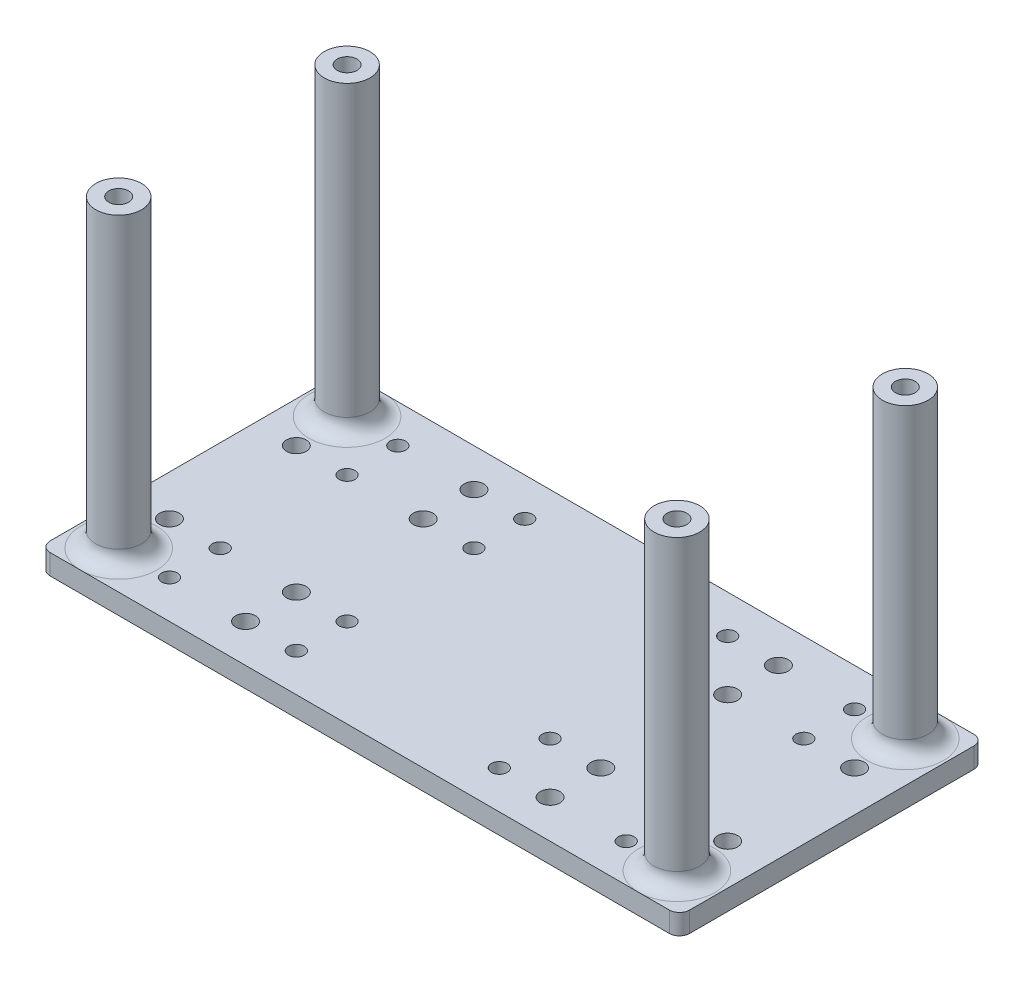
SolidWorks part; units mm, degrees
ref_plane "Front Plane" through (0, 0, 0) normal (0, 0, 1) x (1, 0, 0)
ref_plane "Top Plane" through (0, 0, 0) normal (0, 1, 0) x (1, 0, 0)
ref_plane "Right Plane" through (0, 0, 0) normal (1, 0, 0) x (0, 0, -1)
sketch "Sketch3" plane through (0, 0, 0) normal (0, 1, 0) x (1, 0, 0)
  line L1 (-63, -30) -> (63, -30)
  line L2 (-63, -30) -> (-63, 30)
  line L3 (-63, 30) -> (63, 30)
  line L4 (63, -30) -> (63, 30)
  line L5 (-63, -30) -> (63, 30) construction
  line L6 (-63, 30) -> (63, -30) construction
  point P0 (0, 0)
  dimension "D1" = 126
  dimension "D2" = 60
extrude "Boss-Extrude1" add sketch "Sketch3" along normal blind 4
sketch "Sketch4" plane through (0, 0, 0) normal (0, 1, 0) x (1, 0, 0)
  line L1 (-55, -22.5) -> (55, -22.5) construction
  line L2 (-55, -22.5) -> (-55, 22.5) construction
  line L3 (-55, 22.5) -> (55, 22.5) construction
  line L4 (55, -22.5) -> (55, 22.5) construction
  line L5 (-55, -22.5) -> (55, 22.5) construction
  line L6 (-55, 22.5) -> (55, -22.5) construction
  circle A0 centre (-55, 22.5) radius 1.95
  circle A1 centre (-45, 22.5) radius 1.55
  point P0 (0, 0)
  dimension "D3" = 3.9
  dimension "D5" = 3.1
  dimension "D1" = 45
  dimension "D2" = 110
  dimension "D4" = 10
extrude "Cut-Extrude1" cut sketch "Sketch4" along normal through all
pattern_linear "LPattern1" count 2 spacing 25 along (1, 0, 0) count 2 spacing 10 along (0, 0, 1) of "Cut-Extrude1"
mirror "Mirror1" about plane through (0, 0, 0) normal (1, 0, 0) of "LPattern1", "Cut-Extrude1" second plane through (0, 0, 0) second plane normal (0, 0, 1)
fillet "Fillet1" radius 2 4 edges at (63, 2, -30) (63, 2, 30) (-63, 2, -30) (-63, 2, 30)
sketch "Sketch5" plane through (0, 0, 0) normal (0, 1, 0) x (1, 0, 0)
  circle A0 centre (-55, 22.5) radius 4.5
  dimension "D1" = 9
extrude "Boss-Extrude2" add sketch "Sketch5" along normal blind 60 from surface at 4 starting at face at (55, 4, 10.55)
mirror "Mirror2" about plane through (0, 0, 0) normal (1, 0, 0) of "Boss-Extrude2" second plane through (0, 0, 0) second plane normal (0, 0, 1)
fillet "Fillet2" radius 3 4 edges at (-55, 4, -27) (-55, 4, 18) (55, 4, -27) (55, 4, 18)
sketch "Sketch6" plane through (0, 64, 0) normal (0, 1, 0) x (1, 0, 0)
  circle A0 centre (-55, 22.5) radius 1.95
  dimension "D1" = 3.9
extrude "Cut-Extrude2" cut sketch "Sketch6" against normal blind 10 contours A0
mirror "Mirror3" about plane through (0, 0, 0) normal (0, 0, 1) of "Cut-Extrude2" second plane through (0, 0, 0) second plane normal (1, 0, 0)
sketch "Sketch7" plane through (0, 0, 0) normal (0, 1, 0) x (1, 0, 0)
  circle A0 centre (55, -22.5) radius 1.95 construction
  circle A1 centre (55, 22.5) radius 1.95 construction
  circle A2 centre (-55, -22.5) radius 1.95 construction
  circle A3 centre (-55, 22.5) radius 1.95 construction
  circle A4 centre (55, -22.5) radius 1.95
  circle A5 centre (55, 22.5) radius 1.95
  circle A6 centre (-55, -22.5) radius 1.95
  circle A7 centre (-55, 22.5) radius 1.95
extrude "Cut-Extrude3" cut sketch "Sketch7" along normal blind 10
